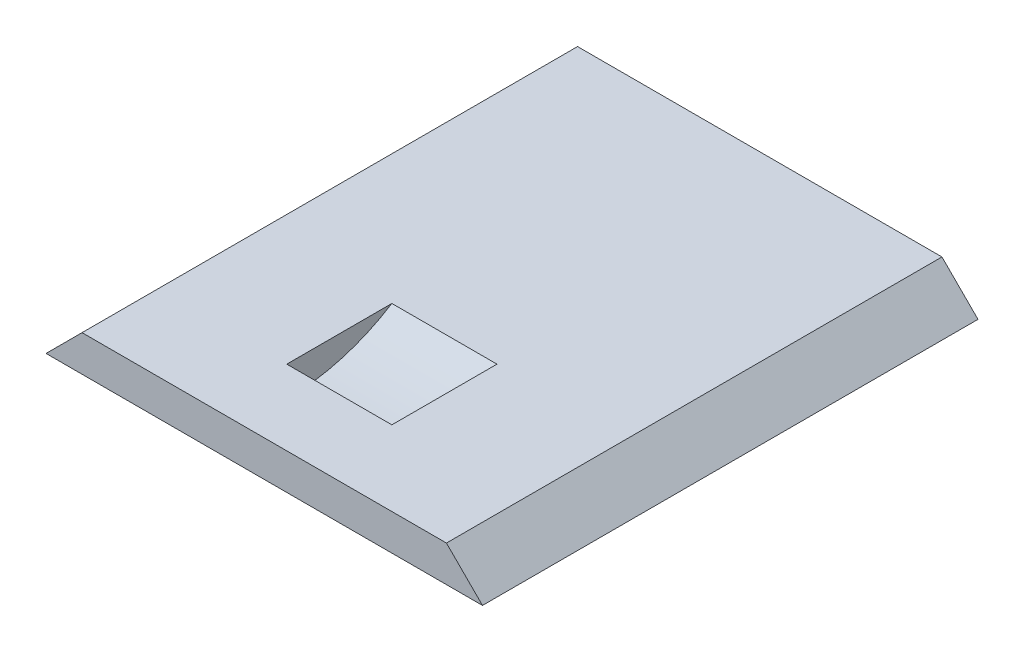
SolidWorks part; units mm, degrees
ref_plane "Front Plane" through (0, 0, 0) normal (0, 0, 1) x (1, 0, 0)
ref_plane "Top Plane" through (0, 0, 0) normal (0, 1, 0) x (1, 0, 0)
ref_plane "Right Plane" through (0, 0, 0) normal (1, 0, 0) x (0, 0, -1)
sketch "Sketch1" plane through (0, 0, 0) normal (0, 0, 1) x (1, 0, 0)
  line L0 (15.5, 0) -> (-15.5, 0) construction
  line L1 (-15.5, 0) -> (-12.5, 3) construction
  line L2 (-12.5, 3) -> (12.5, 3) construction
  line L3 (12.5, 3) -> (15.5, 0) construction
  line L4 (-12.1343, 2.8) -> (-14.5343, 0.4)
  line L5 (-14.5343, 0.4) -> (14.5343, 0.4)
  line L6 (14.5343, 0.4) -> (12.1343, 2.8)
  line L7 (12.1343, 2.8) -> (-12.1343, 2.8)
  point P4 (0, 0)
  dimension "D1" = 25
  dimension "D2" = 45
  dimension "D3" = 3
  dimension "D5" = 31
  dimension "D6" = 0.2
  dimension "D7" = 0.4
  dimension "D8" = 0.4
  dimension "D9" = 0.4
extrude "Boss-Extrude1" add sketch "Sketch1" against normal blind 33
sketch "Sketch2" plane through (0, 2.8, 0) normal (0, 1, 0) x (1, 0, 0)
  line L0 (12.1343, 0) -> (-12.1343, 0) construction
  line L1 (-3.5, 12) -> (3.5, 12)
  line L2 (-3.5, 12) -> (-3.5, 5)
  line L3 (-3.5, 5) -> (3.5, 5)
  line L4 (3.5, 12) -> (3.5, 5)
  line L5 (-3.5, 12) -> (3.5, 5) construction
  line L6 (-3.5, 5) -> (3.5, 12) construction
  point P4 (0, 8.5)
  dimension "D1" = 7
  dimension "D2" = 7
  dimension "D3" = 5
extrude "Cut-Extrude1" cut sketch "Sketch2" against normal blind 2
fillet "Fillet1" radius 13 1 edges at (0, 0.8, -12)
